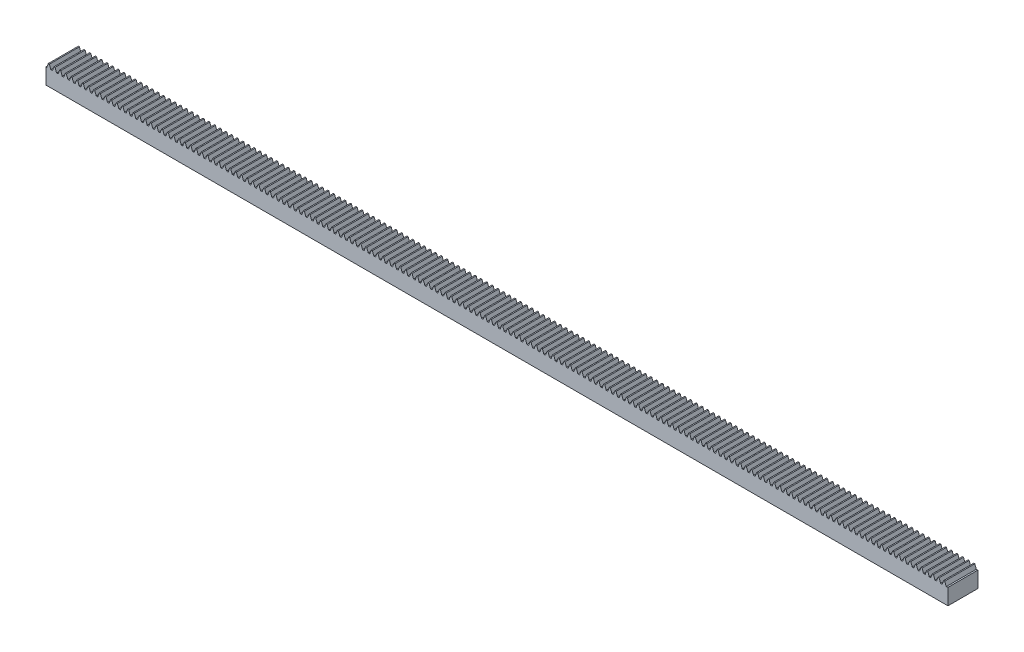
SolidWorks part; units mm, degrees
extrude "Blank" add sketch "BlankSke" against normal blind 10
sketch "BlankSke" plane through (0, 0, 0) normal (0, 0, 1) x (1, 0, 0)
  line L1 (0, 0) -> (300, 0)
  line L2 (0, 0) -> (0, 6.6)
  line L3 (0, 6.6) -> (300, 6.6)
  line L4 (300, 0) -> (300, 6.6)
  dimension "Length" = 300
ref_plane "Plane1" through (0, 0, 0) normal (0, 0, 1) x (1, 0, 0)
ref_plane "Plane2" through (0, 0, 0) normal (0, 1, 0) x (1, 0, 0)
ref_plane "Plane3" through (0, 0, 0) normal (1, 0, 0) x (0, 0, -1)
sketch "HoldingSke" plane through (0, 0, 0) normal (0, 1, 0) x (1, 0, 0)
  line L0 (0, 0) -> (0.232, 1.6504)
  line L1 (-15, 0) -> (100, 0) construction
  line L2 (0, 0) -> (-2.1039, 2.3779)
  line L3 (0, 0) -> (-11.863, 4.5341)
  line L4 (0, 0) -> (-8.1655, 2.8116)
  line L5 (0, 0) -> (-23.7986, -8.8762)
  line L6 (0, 0) -> (-10.5278, -7.1032)
  line L9 (-71.009, 38.7566) -> (210.8988, 141.3627)
  line L10 (-76.2, 2.9779) -> (-70.2, 2.9779)
  line L11 (0, 0) -> (-10, 0)
  line L12 (-76.2, 101.6) -> (-76.177, 101.6)
  line L13 (24.9733, 27.94) -> (52.9518, 28.4284)
  line L14 (24.9733, 27.94) -> (24.9743, 27.94)
  line L15 (24.9733, 27.94) -> (100.4006, 29.5858)
  circle A0 centre (0, 0) radius 19.05
  circle A1 centre (0, 0) radius 3
  circle A2 centre (0, 0) radius 12.7
  dimension "Num_teeth" = 161
  dimension "Width" = 10
  dimension "Length" = 300
  dimension "Pitch_height" = 6
sketch "TooCutSkeIll" plane through (0, 0, 0) normal (0, 0, 1) x (1, 0, 0)
  line L0 (-0.7529, 6.5842) -> (-0.3034, 5.3494)
  line L1 (-0.1615, 5.25) -> (0.1615, 5.25)
  line L2 (0.3034, 5.3494) -> (0.7529, 6.5842)
  line L3 (300, 6.6) -> (0, 6.6) construction
  line L4 (0, 0) -> (0, 64.897) construction
  line L5 (-13.208, 6) -> (12.954, 6) construction
  line L6 (0, 0) -> (300, 0) construction
  line L7 (0.5402, 6) -> (0.5402, 48.7463) construction
  line L8 (-0.5402, 6) -> (-0.5402, 48.7463) construction
  line L9 (0.7754, 6.6) -> (0.7754, 6.6254)
  line L10 (-0.7754, 6.6) -> (-0.7754, 6.6254)
  line L11 (-0.7754, 6.6254) -> (0.7754, 6.6254)
  arc A0 (0.1615, 5.25) -> (0.3034, 5.3494) centre (0.1615, 5.401) ccw
  arc A1 (-0.3034, 5.3494) -> (-0.1615, 5.25) centre (-0.1615, 5.401) ccw
  arc A2 (0.7754, 6.6) -> (0.7529, 6.5842) centre (0.7754, 6.576) ccw
  arc A3 (-0.7529, 6.5842) -> (-0.7754, 6.6) centre (-0.7754, 6.576) ccw
  dimension "Addendum_plus" = 0.6254
  dimension "Pitch_height" = 6
  dimension "Pressure_angle" = 20
  dimension "Gap_width" = 1.0805
  dimension "Dedendum" = 0.75
extrude "ToothCutIll" [suppressed] cut sketch "TooCutSkeIll" against normal through all
sketch "TooCutSkeSim" plane through (0, 0, 0) normal (0, 0, 1) x (1, 0, 0)
  line L0 (0.2673, 5.25) -> (-0.2673, 5.25)
  line L1 (0.7679, 6.6254) -> (0.2673, 5.25)
  line L2 (0, 17.4625) -> (0, 53.467) construction
  line L3 (0.7679, 6.6254) -> (-0.7679, 6.6254)
  line L6 (-0.7679, 6.6254) -> (-0.2673, 5.25)
  line L9 (-0.5402, 6) -> (0.5402, 6) construction
  line L10 (0, 0) -> (300, 0) construction
  line L11 (0.5402, 6) -> (0.5402, 53.467) construction
  line L12 (-0.5402, 6) -> (-0.5402, 53.467) construction
  dimension "Addendum_plus" = 0.6254
  dimension "Pitch_height" = 6
  dimension "Pressure_angle" = 20
  dimension "Gap_width" = 1.0805
  dimension "Dedendum" = 0.75
extrude "ToothCutSim" cut sketch "TooCutSkeSim" against normal through all
pattern_linear "TeethCuts" count 161 spacing 1.885 along (1, 0, 0) of "ToothCutIll", "ToothCutSim"
equation "' \"Module@HoldingSke\" = 6.35"
equation "' \"Num_teeth@HoldingSke\" = 12"
equation "' \"Ap@HoldingSke\" =  20"
equation "' \"Ap@HoldingSke\" = 20"
equation "' \"Width@HoldingSke\" = 0.25 * 25.4"
equation "' \"Show_teeth@HoldingSke\" = 500"
equation "' \"Backlash@HoldingSke\" = 0.009 * 25.4"
equation "' \"Addendum_fac@HoldingSke\" = 1.0"
equation "' \"Dedendum_fac@HoldingSke\" = 1.25"
equation "' \"Dedendum_add@HoldingSke\" = 0.00005 * 25.4"
equation "' \"Clearance_fac@HoldingSke\" = 0.25"
equation "' \"Pitch_height@HoldingSke\" = 1 * 25.4"
equation "' \"Length@HoldingSke\" = 4.71 * 25.4"
equation "\"Pitch@HoldingSke\" = 1 / \"Module@HoldingSke\""
equation "\"MPH@HoldingSke\" = \"Dedendum_fac@HoldingSke\" / \"Pitch@HoldingSke\" + 2 * \"Dedendum_add@HoldingSke\" + 0.002 * 25.4"
equation "\"MPH@HoldingSke\" = ((sgn( \"MPH@HoldingSke\" - \"Pitch_height@HoldingSke\")+1)*( \"MPH@HoldingSke\" - \"Pitch_height@HoldingSke\"))/2 + \"Pitch_height@HoldingSke\""
equation "\"Blank_height@BlankSke\" = \"Pitch_height@HoldingSke\" + \"Addendum_fac@HoldingSke\"  / \"Pitch@HoldingSke\" "
equation "\"Length@BlankSke\" =  \"Length@HoldingSke\""
equation "\"Face_width@Blank\" = \"Width@HoldingSke\""
equation "\"Pressure_angle@TooCutSkeIll\" = \"Ap@HoldingSke\""
equation "\"Addendum_plus@TooCutSkeIll\" =  \"Addendum_fac@HoldingSke\"  / \"Pitch@HoldingSke\" + 0.001 *25.4"
equation "\"Dedendum@TooCutSkeIll\" = \"Dedendum_fac@HoldingSke\"  / \"Pitch@HoldingSke\""
equation "\"Pitch_height@TooCutSkeIll\" =  \"MPH@HoldingSke\""
equation "\"Gap_width@TooCutSkeIll\" = 3.14159265 / 2 / \"Pitch@HoldingSke\" + 6 * \"Backlash@HoldingSke\""
equation "\"Pressure_angle@TooCutSkeSim\" = \"Ap@HoldingSke\""
equation "\"Addendum_plus@TooCutSkeSim\" =  \"Addendum_fac@HoldingSke\"  / \"Pitch@HoldingSke\" + 0.001 * 25.4"
equation "\"Dedendum@TooCutSkeSim\" = \"Dedendum_fac@HoldingSke\"  / \"Pitch@HoldingSke\""
equation "\"Pitch_height@TooCutSkeSim\" =  \"MPH@HoldingSke\""
equation "\"Gap_width@TooCutSkeSim\" = 3.14159265 / 2 / \"Pitch@HoldingSke\" + 6 * \"Backlash@HoldingSke\""
equation "\"Root_fillet@TooCutSkeIll\" = \"Clearance_fac@HoldingSke\" / \"Pitch@HoldingSke\" + \"Dedendum_add@HoldingSke\""
equation "\"Break_rad@TooCutSkeIll\" = 0.02 / \"Pitch@HoldingSke\" * 2"
equation "\"Linear_pitch@TeethCuts\" = 3.14159265 / \"Pitch@HoldingSke\""
equation "\"Num_teeth@HoldingSke\" = int( ( \"Length@HoldingSke\" + 0 ) / (3.14159265 / \"Pitch@HoldingSke\")) + 0.9999  + 1"
equation " \"Num_teeth@TeethCuts\" = int( \"Show_teeth@HoldingSke\" ) + 1"
equation " \"Num_teeth@TeethCuts\" = ((sgn( \"Num_teeth@TeethCuts\" - \"Num_teeth@HoldingSke\" )-1)*( \"Num_teeth@TeethCuts\" - \"Num_teeth@HoldingSke\" ))/-2+ \"Num_teeth@HoldingSke\""
equation " \"Num_teeth@TeethCuts\" = ((sgn( \"Num_teeth@TeethCuts\" - 2.0)+1)*( \"Num_teeth@TeethCuts\" - 2.0))/2 +2.0"
